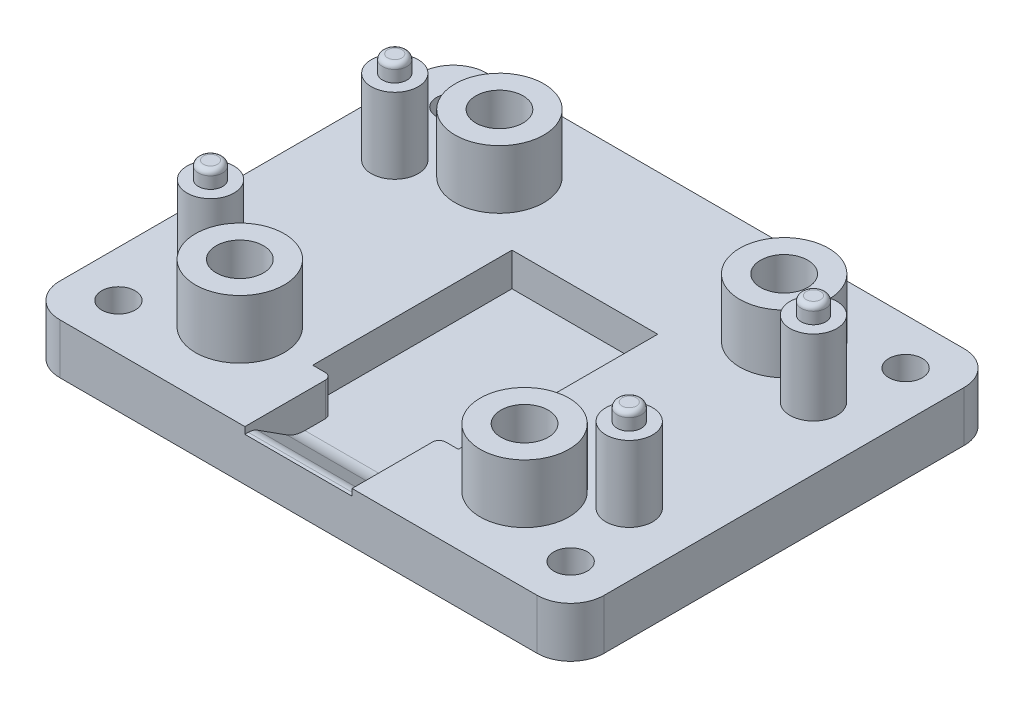
SolidWorks part; units mm, degrees
material "尼龙 101"
ref_plane "前视基准面" through (0, 0, 0) normal (0, 0, 1) x (1, 0, 0)
ref_plane "上视基准面" through (0, 0, 0) normal (0, 1, 0) x (1, 0, 0)
ref_plane "右视基准面" through (0, 0, 0) normal (1, 0, 0) x (0, 0, -1)
other "Configuration Table"
sketch "草图1" plane through (0, 0, 0) normal (0, 1, 0) x (1, 0, 0)
  line L1 (-16.25, 12.75) -> (16.25, 12.75)
  line L2 (-16.25, 12.75) -> (-16.25, -12.75)
  line L3 (-16.25, -12.75) -> (16.25, -12.75)
  line L4 (16.25, 12.75) -> (16.25, -12.75)
  line L5 (-16.25, 12.75) -> (16.25, -12.75) construction
  line L6 (-16.25, -12.75) -> (16.25, 12.75) construction
  point P0 (0, 0)
  dimension "D1" = 32.5
  dimension "D2" = 25.5
extrude "凸台-拉伸1" add sketch "草图1" along normal blind 3
sketch "草图2" plane through (0, 3, 0) normal (0, 1, 0) x (1, 0, 0)
  line L0 (0, 0) -> (0, 5.35) construction
  line L1 (-5.35, 5.35) -> (5.35, 5.35)
  line L2 (5.35, 5.35) -> (5.35, -7.55)
  line L3 (5.35, -7.55) -> (4.35, -7.55)
  line L4 (4.35, -7.55) -> (4.35, 4.35)
  line L5 (4.35, 4.35) -> (-4.35, 4.35)
  line L6 (-4.35, -7.55) -> (-4.35, 4.35)
  line L7 (-5.35, -7.55) -> (-4.35, -7.55)
  line L8 (-5.35, 5.35) -> (-5.35, -7.55)
  point P9 (0, 4.35)
  dimension "D1" = 8.7
  dimension "D2" = 11.9
  dimension "D3" = 4.35
  dimension "D4" = 1
  dimension "D5" = 1
extrude "凸台-拉伸2" add sketch "草图2" along normal blind 1.5
sketch "草图5" plane through (0, 3, 0) normal (0, 1, 0) x (1, 0, 0)
  line L0 (0, 12.75) -> (0, 0) construction
  line L1 (16.25, 12.75) -> (-16.25, 12.75) construction
  line L2 (0, 0) -> (16.25, 0) construction
  line L3 (16.25, -12.75) -> (16.25, 12.75) construction
  circle A0 centre (12.5, 5.5) radius 1.4
  circle A1 centre (12.5, -5.5) radius 1.4
  circle A2 centre (-12.5, -5.5) radius 1.4
  circle A3 centre (-12.5, 5.5) radius 1.4
  dimension "D1" = 2.8
  dimension "D2" = 25
  dimension "D3" = 11
extrude "凸台-拉伸3" add sketch "草图5" along normal blind 4.5
sketch "草图6" plane through (0, 7.5, 0) normal (0, 1, 0) x (1, 0, 0)
  circle A0 centre (-12.5, -5.5) radius 0.725
  circle A1 centre (-12.5, 5.5) radius 0.725
  circle A2 centre (12.5, 5.5) radius 0.725
  circle A3 centre (12.5, -5.5) radius 0.725
  dimension "D1" = 1.45
extrude "凸台-拉伸4" add sketch "草图6" along normal blind 1
sketch "草图7" plane through (0, 3, 0) normal (0, 1, 0) x (1, 0, 0)
  line L0 (0, 0) -> (0, 12.75) construction
  line L1 (16.25, 12.75) -> (-16.25, 12.75) construction
  line L2 (0, 0) -> (16.25, 0) construction
  line L3 (16.25, -12.75) -> (16.25, 12.75) construction
  circle A0 centre (13.5, 10) radius 1
  circle A1 centre (-13.5, 10) radius 1
  circle A2 centre (-13.5, -10) radius 1
  circle A3 centre (13.5, -10) radius 1
  dimension "D1" = 2
  dimension "D2" = 20
  dimension "D3" = 27
extrude "切除-拉伸1" cut sketch "草图7" against normal blind 10
sketch "草图8" plane through (0, 0, 0) normal (0, -1, 0) x (1, 0, 0)
  circle A0 centre (-13.5, 10) radius 2
  circle A1 centre (13.5, 10) radius 2
  circle A2 centre (13.5, -10) radius 2
  circle A3 centre (-13.5, -10) radius 2
  dimension "D1" = 4
extrude "切除-拉伸2" cut sketch "草图8" against normal blind 1
fillet "圆角1" radius 2 4 edges at (-16.25, 1.5, -12.75) (16.25, 1.5, -12.75) (-16.25, 1.5, 12.75) (16.25, 1.5, 12.75)
sketch "草图9" plane through (0, 3, 0) normal (0, 1, 0) x (1, 0, 0)
  line L0 (0, 12.75) -> (0, 0) construction
  line L1 (14.25, 12.75) -> (-14.25, 12.75) construction
  line L2 (0, 0) -> (16.25, 0) construction
  line L3 (16.25, -10.75) -> (16.25, 10.75) construction
  circle A0 centre (8.5, 7.75) radius 2.65
  circle A1 centre (-8.5, 7.75) radius 2.65
  circle A2 centre (-8.5, -7.75) radius 2.65
  circle A3 centre (8.5, -7.75) radius 2.65
  dimension "D1" = 17
  dimension "D2" = 15.5
  dimension "D3" = 5.3
extrude "凸台-拉伸5" add sketch "草图9" along normal blind 3.5
sketch "草图11" plane through (0, 6.5, 0) normal (0, 1, 0) x (1, 0, 0)
  circle A0 centre (-8.5, 7.75) radius 1.05
  circle A1 centre (-8.5, -7.75) radius 1.05
  circle A2 centre (8.5, -7.75) radius 1.05
  circle A3 centre (8.5, 7.75) radius 1.05
  dimension "D1" = 2.1
extrude "切除-拉伸4" cut sketch "草图11" against normal blind 100
sketch "草图12" plane through (0, 6.5, 0) normal (0, 1, 0) x (1, 0, 0)
  circle A0 centre (-8.5, 7.75) radius 1.41
  circle A1 centre (8.5, 7.75) radius 1.41
  circle A2 centre (-8.5, -7.75) radius 1.41
  circle A3 centre (8.5, -7.75) radius 1.41
  dimension "D1" = 2.82
extrude "切除-拉伸5" cut sketch "草图12" against normal blind 5.5
fillet "圆角2" radius 0.3 4 edges at (12.5, 8.5, -4.775) (12.5, 8.5, 6.225) (-12.5, 8.5, 6.225) (-12.5, 8.5, -4.775)
sketch "草图15" plane through (0, 3, 0) normal (0, 1, 0) x (1, 0, 0)
  line L0 (0, 0) -> (0, 12.75) construction
  line L1 (14.25, 12.75) -> (-14.25, 12.75) construction
  line L2 (-4.35, 4.35) -> (4.35, 4.35)
  line L3 (4.35, 4.35) -> (4.35, -7.55)
  line L4 (4.35, -7.55) -> (3.2, -7.55)
  line L5 (3.2, -7.55) -> (3.2, -12.75)
  line L6 (-14.25, -12.75) -> (14.25, -12.75) construction
  line L7 (3.2, -12.75) -> (-3.2, -12.75)
  line L8 (-3.2, -7.55) -> (-3.2, -12.75)
  line L9 (-4.35, -7.55) -> (-3.2, -7.55)
  line L10 (-4.35, 4.35) -> (-4.35, -7.55)
  line L11 (4.35, 4.35) -> (4.35, -7.55) construction
  point P14 (0, -12.75)
  point P17 (0, 4.35)
  dimension "D1" = 6.4
extrude "切除-拉伸8" cut sketch "草图15" against normal blind 2
sketch "草图17" plane through (0, 4.5, 0) normal (0, 1, 0) x (1, 0, 0)
  line L8 (-4.35, -7.55) -> (-4.35, 4.35)
  line L9 (-4.35, 4.35) -> (4.35, 4.35)
  line L10 (4.35, 4.35) -> (4.35, -7.55)
  line L11 (4.35, -7.55) -> (5.35, -7.55)
  line L12 (5.35, -7.55) -> (5.35, 5.35)
  line L13 (5.35, 5.35) -> (-5.35, 5.35)
  line L14 (-5.35, 5.35) -> (-5.35, -7.55)
  line L15 (-5.35, -7.55) -> (-4.35, -7.55)
  line L16 (-4.35, -7.55) -> (-4.35, 4.35)
  line L17 (-4.35, 4.35) -> (4.35, 4.35)
  line L18 (4.35, 4.35) -> (4.35, -7.55)
  line L19 (4.35, -7.55) -> (5.35, -7.55)
  line L20 (5.35, -7.55) -> (5.35, 5.35)
  line L21 (5.35, 5.35) -> (-5.35, 5.35)
  line L22 (-5.35, 5.35) -> (-5.35, -7.55)
  line L23 (-5.35, -7.55) -> (-4.35, -7.55)
  dimension "D1" = 0
extrude "切除-拉伸9" cut sketch "草图17" against normal blind 1.5
sketch "草图18" plane through (3.2, 0, 0) normal (-1, 0, 0) x (0, 0, 1)
  line L0 (12.75, 1) -> (9.75, 1)
  line L2 (12.75, 1) -> (12.75, 3) construction
  line L3 (12.75, 2.6) -> (12.75, 1)
  line L5 (12.75, 3) -> (12.75, 0) construction
  line L6 (12.75, 2.6) -> (12.25, 2.6)
  line L7 (12.25, 2.6) -> (9.75, 1)
  line L8 (12.75, 3) -> (10.75, 3) construction
  dimension "D1" = 3
  dimension "D2" = 0.4
  dimension "D3" = 0.5
extrude "凸台-拉伸6" add sketch "草图18" along normal up to surface (6.4 mm away) up to face at (-3.2, 2, 10.15)
fillet "圆角3" radius 2 1 edges at (0, 1, 9.75)
fillet "圆角5" radius 1 1 edges at (0, 2.6, 12.25)
fillet "圆角6" radius 0.4 2 edges at (3.2, 2, 7.55) (-3.2, 2, 7.55)
